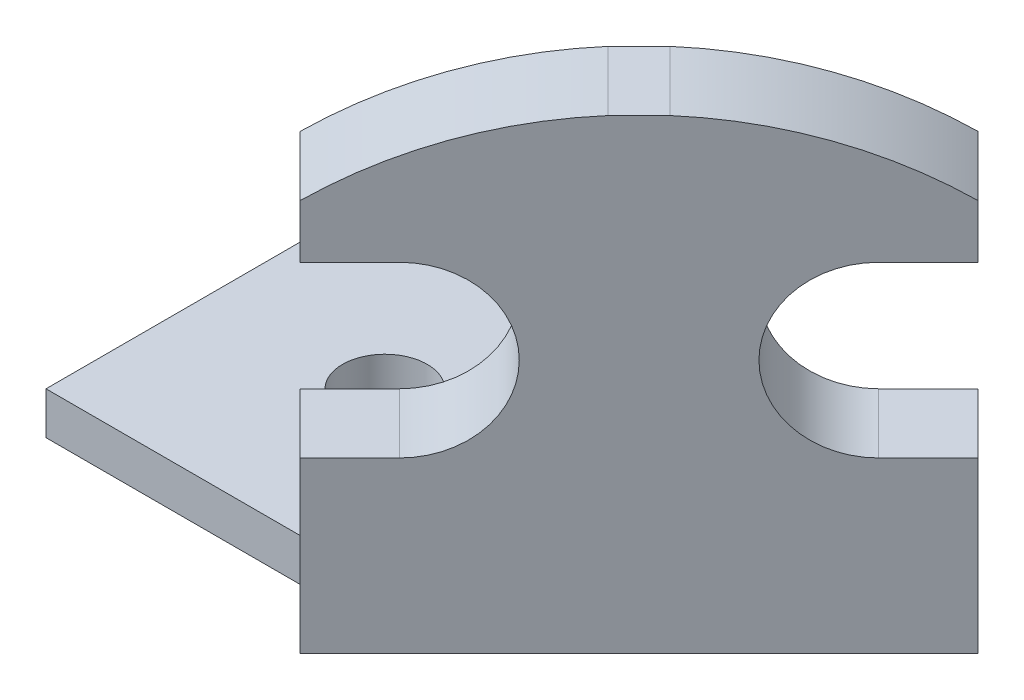
SolidWorks part; units mm, degrees
ref_plane "Front Plane" through (0, 0, 0) normal (0, 0, 1) x (1, 0, 0)
ref_plane "Top Plane" through (0, 0, 0) normal (0, 1, 0) x (1, 0, 0)
ref_plane "Right Plane" through (0, 0, 0) normal (1, 0, 0) x (0, 0, -1)
sketch "Sketch1" plane through (0, 0, 0) normal (0, 1, 0) x (1, 0, 0)
  line L0 (0, 0) -> (0, 80)
  line L1 (0, 80) -> (140, 80)
  line L2 (140, 80) -> (60, 0)
  line L3 (60, 0) -> (0, 0)
  line L4 (154.1421, 65.8579) -> (74.1421, -14.1421)
  line L5 (60, 0) -> (74.1421, -14.1421)
  line L6 (140, 80) -> (154.1421, 65.8579)
  circle A0 centre (40, 40) radius 10
  dimension "D6" = 20
  dimension "D1" = 80
  dimension "D2" = 60
  dimension "D3" = 135
  dimension "D5" = 40
  dimension "D7" = 40
  dimension "D4" = 20
extrude "Boss-Extrude1" add sketch "Sketch1" along normal blind 10 contours L3 L2 L1 L0 A0 region at (53.1844, 0, -45.5513)
extrude "Boss-Extrude2" add sketch "Sketch1<3>" along normal blind 110 contours L6 L2 L5 L4 region at (107.0711, 0, -32.9289)
sketch "Sketch1<3>" plane through (0, 0, 0) normal (0, 1, 0) x (1, 0, 0) same geometry as "Sketch1"
sketch "Sketch2" plane through (44.1421, 0, 44.1421) normal (0.7071, 0, 0.7071) x (0.7071, 0, -0.7071)
  line L0 (42.4264, 10) -> (155.5635, 10) construction
  line L1 (42.4264, 110) -> (42.4264, 0) construction
  line L2 (155.5635, 110) -> (155.5635, 0) construction
  line L3 (155.5635, 0) -> (42.4264, 0) construction
  line L4 (42.4264, 92.6254) -> (42.4264, 80)
  line L5 (155.5635, 92.6254) -> (155.5635, 80)
  line L6 (98.9949, 10) -> (98.9949, 93.3304) construction
  line L7 (58.9949, 60) -> (98.9949, 93.3304) construction
  line L8 (138.9949, 60) -> (98.9949, 93.3304) construction
  line L9 (42.4264, 40) -> (42.4264, 10)
  line L10 (155.5635, 40) -> (155.5635, 10)
  line L11 (58.9949, 80) -> (42.4264, 80)
  line L12 (58.9949, 40) -> (42.4264, 40)
  line L13 (138.9949, 40) -> (155.5635, 40)
  line L14 (138.9949, 80) -> (155.5635, 80)
  arc A0 (155.5635, 92.6254) -> (42.4264, 92.6254) centre (98.9949, 10) ccw
  arc A1 (58.9949, 40) -> (58.9949, 80) centre (58.9949, 60) ccw
  arc A2 (138.9949, 40) -> (138.9949, 80) centre (138.9949, 60) cw
  line M9 (155.5635, 0) -> (155.5635, 110)
  line M10 (155.5635, 110) -> (42.4264, 110)
  line M11 (42.4264, 110) -> (42.4264, 0)
  dimension "D3" = 40
  dimension "D1" = 10
  dimension "D2" = 60
  dimension "D4" = 80
extrude "Cut-Extrude2" cut sketch "Sketch2" against normal blind 110 and the other way through all contours A0 M10 M11 | A0 M9 M10 | L12 A1 L11 M11 | A2 L13 L14 M9 region at (85.7719, 60, 2.5124) region at (83.7522, 104.8538, 4.5321) region at (142.5124, 60, -54.2281) region at (144.5321, 104.8538, -56.2478)
